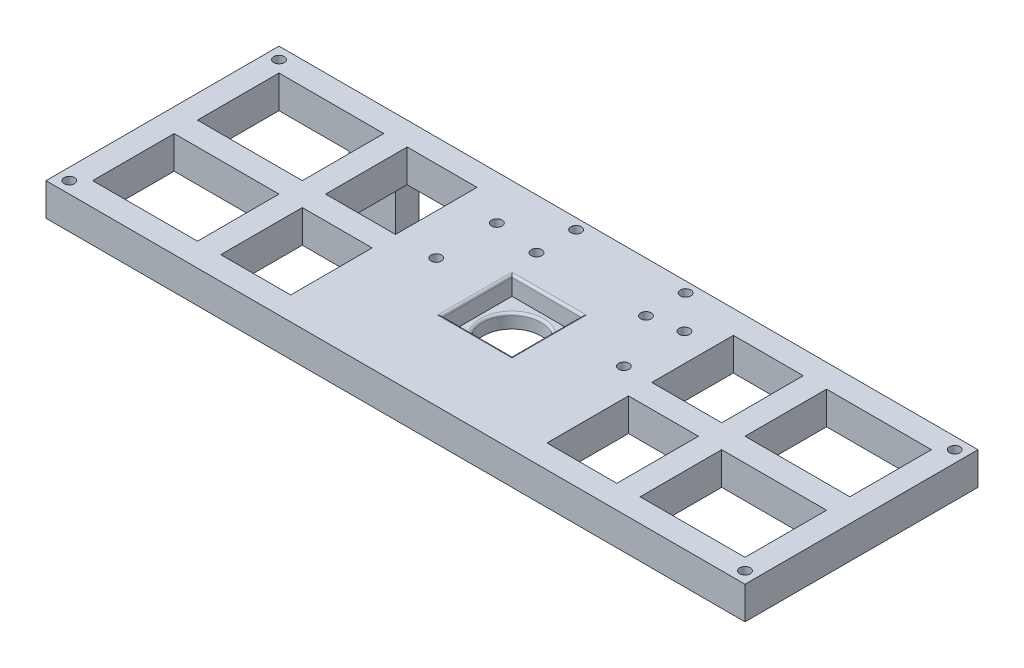
SolidWorks part; units mm, degrees
ref_plane "前视基准面" through (0, 0, 0) normal (0, 0, 1) x (1, 0, 0)
ref_plane "上视基准面" through (0, 0, 0) normal (0, 1, 0) x (1, 0, 0)
ref_plane "右视基准面" through (0, 0, 0) normal (1, 0, 0) x (0, 0, -1)
sketch "草图1" plane through (0, 0, 0) normal (0, 1, 0) x (1, 0, 0)
  line L1 (0, 0) -> (-300, 0)
  line L2 (0, 0) -> (0, 100)
  line L3 (0, 100) -> (-300, 100)
  line L4 (-300, 0) -> (-300, 100)
  dimension "D1" = 300
  dimension "D2" = 100
extrude "凸台-拉伸1" add sketch "草图1" along normal blind 16
sketch "草图2" plane through (0, 16, 0) normal (0, 1, 0) x (1, 0, 0)
  line L0 (-150, 100) -> (-150, 50) construction
  line L1 (0, 100) -> (-300, 100) construction
  line L2 (-300, 50) -> (-150, 50) construction
  line L3 (-300, 100) -> (-300, 0) construction
  line L5 (-165, 65) -> (-135, 65)
  line L6 (-165, 65) -> (-165, 35)
  line L7 (-165, 35) -> (-135, 35)
  line L8 (-135, 65) -> (-135, 35)
  line L9 (-165, 65) -> (-135, 35) construction
  line L10 (-165, 35) -> (-135, 65) construction
  dimension "D1" = 50
  dimension "D2" = 30
  dimension "D3" = 30
extrude "切除-拉伸1" cut sketch "草图2" against normal blind 8
sketch "草图3" plane through (0, 8, 0) normal (0, 1, 0) x (1, 0, 0)
  line L0 (-135, 65) -> (-165, 65) construction
  line L1 (-135, 35) -> (-135, 65) construction
  circle A0 centre (-150, 50) radius 12.5
  dimension "D3" = 25
  dimension "D1" = 15
  dimension "D2" = 15
extrude "切除-拉伸2" cut sketch "草图3" against normal blind 14
sketch "草图4" plane through (0, 16, 0) normal (0, 1, 0) x (1, 0, 0)
  line L0 (-165, 65) -> (-165, 35) construction
  line L1 (-295, 90) -> (-245, 90)
  line L2 (-295, 90) -> (-295, 55)
  line L3 (-295, 55) -> (-245, 55)
  line L4 (-245, 90) -> (-245, 55)
  line L5 (-295, 45) -> (-245, 45)
  line L6 (-295, 45) -> (-295, 10)
  line L7 (-295, 10) -> (-245, 10)
  line L8 (-245, 45) -> (-245, 10)
  line L9 (-235, 90) -> (-185, 90)
  line L10 (-235, 90) -> (-235, 55)
  line L11 (-235, 55) -> (-185, 55)
  line L12 (-185, 90) -> (-185, 55)
  line L13 (-235, 45) -> (-185, 45)
  line L14 (-235, 45) -> (-235, 10)
  line L15 (-235, 10) -> (-185, 10)
  line L16 (-185, 45) -> (-185, 10)
  line L17 (0, 100) -> (-300, 100) construction
  line L18 (-300, 0) -> (0, 0) construction
  line L19 (-300, 100) -> (-300, 0) construction
  line L20 (-150, 100) -> (-150, 73.2626) construction
  line L21 (-5, 10) -> (-55, 10)
  line L22 (-55, 45) -> (-55, 10)
  line L23 (-5, 45) -> (-55, 45)
  line L24 (-5, 45) -> (-5, 10)
  line L25 (-65, 10) -> (-115, 10)
  line L26 (-115, 45) -> (-115, 10)
  line L27 (-65, 45) -> (-115, 45)
  line L28 (-65, 45) -> (-65, 10)
  line L29 (-65, 55) -> (-115, 55)
  line L30 (-115, 90) -> (-115, 55)
  line L31 (-65, 90) -> (-115, 90)
  line L32 (-65, 90) -> (-65, 55)
  line L33 (-5, 55) -> (-55, 55)
  line L34 (-55, 90) -> (-55, 55)
  line L35 (-5, 90) -> (-55, 90)
  line L36 (-5, 90) -> (-5, 55)
  dimension "D1" = 20
  dimension "D2" = 20
  dimension "D3" = 10
  dimension "D4" = 10
  dimension "D5" = 10
  dimension "D6" = 35
  dimension "D7" = 10
  dimension "D8" = 10
  dimension "D9" = 5
  dimension "D10" = 5
  dimension "D11" = 35
  dimension "D12" = 35
  dimension "D13" = 50
  dimension "D14" = 50
  dimension "D15" = 50
  dimension "D16" = 50
extrude "切除-拉伸3" cut sketch "草图4" against normal up to next
sketch "草图7" plane through (-185, 0, 0) normal (-1, 0, 0) x (0, 0, 1)
  line L0 (-45, 0) -> (-10, 0) construction
  line L1 (-10, 0) -> (-10, 16) construction
  line L2 (-10, 16) -> (-45, 16) construction
  line L3 (-45, 16) -> (-45, 0) construction
  line L4 (-90, 0) -> (-55, 0) construction
  line L5 (-55, 0) -> (-55, 16) construction
  line L6 (-55, 16) -> (-90, 16) construction
  line L7 (-90, 16) -> (-90, 0) construction
  line L8 (-45, 0) -> (-10, 0)
  line L9 (-10, 0) -> (-10, 16)
  line L10 (-10, 16) -> (-45, 16)
  line L11 (-45, 16) -> (-45, 0)
  line L12 (-90, 0) -> (-55, 0)
  line L13 (-55, 0) -> (-55, 16)
  line L14 (-55, 16) -> (-90, 16)
  line L15 (-90, 16) -> (-90, 0)
extrude "凸台-拉伸2" add sketch "草图7" along normal blind 20
sketch "草图8" plane through (-115, 0, 0) normal (1, 0, 0) x (0, 0, -1)
  line L0 (10, 0) -> (45, 0) construction
  line L1 (45, 0) -> (45, 16) construction
  line L2 (45, 16) -> (10, 16) construction
  line L3 (10, 16) -> (10, 0) construction
  line L4 (55, 0) -> (90, 0) construction
  line L5 (90, 0) -> (90, 16) construction
  line L6 (90, 16) -> (55, 16) construction
  line L7 (55, 16) -> (55, 0) construction
  line L8 (10, 0) -> (45, 0)
  line L9 (45, 0) -> (45, 16)
  line L10 (45, 16) -> (10, 16)
  line L11 (10, 16) -> (10, 0)
  line L12 (55, 0) -> (90, 0)
  line L13 (90, 0) -> (90, 16)
  line L14 (90, 16) -> (55, 16)
  line L15 (55, 16) -> (55, 0)
extrude "凸台-拉伸3" add sketch "草图8" along normal blind 20
sketch "草图9" plane through (0, 0, 0) normal (0, -1, 0) x (1, 0, 0)
  line L5 (-295, -90) -> (-245, -90) construction
  line L10 (-260, -90) -> (-240, -90)
  line L20 (-260, -90) -> (-260, -100)
  line L21 (-260, -100) -> (-240, -100)
  line L22 (-240, -90) -> (-240, -100)
  line L23 (0, -100) -> (-300, -100) construction
  line L24 (-300, -100) -> (-300, 0) construction
  dimension "D3" = 20
  dimension "D4" = 40
extrude "凸台-拉伸4" add sketch "草图9" along normal blind 25
fillet "圆角1" radius 1 1 edges at (-150, 8, -37.5)
fillet "圆角2" radius 1 4 edges at (-135, 16, -50) (-150, 16, -65) (-150, 16, -35) (-165, 16, -50)
sketch "草图13" plane through (-5, 0, 0) normal (-1, 0, 0) x (0, 0, 1)
  line L0 (-90, 0) -> (-55, 0) construction
  line L1 (-55, 0) -> (-55, 16) construction
  line L2 (-55, 16) -> (-90, 16) construction
  line L3 (-90, 16) -> (-90, 0) construction
  line L4 (-45, 0) -> (-10, 0) construction
  line L5 (-10, 0) -> (-10, 16) construction
  line L6 (-10, 16) -> (-45, 16) construction
  line L7 (-45, 16) -> (-45, 0) construction
  line L8 (-90, 0) -> (-55, 0)
  line L9 (-55, 0) -> (-55, 16)
  line L10 (-55, 16) -> (-90, 16)
  line L11 (-90, 16) -> (-90, 0)
  line L12 (-45, 0) -> (-10, 0)
  line L13 (-10, 0) -> (-10, 16)
  line L14 (-10, 16) -> (-45, 16)
  line L15 (-45, 16) -> (-45, 0)
extrude "凸台-拉伸6" add sketch "草图13" along normal blind 4
sketch "草图14" plane through (-295, 0, 0) normal (1, 0, 0) x (0, 0, -1)
  line L0 (55, 0) -> (90, 0) construction
  line L1 (90, 0) -> (90, 16) construction
  line L2 (90, 16) -> (55, 16) construction
  line L3 (55, 16) -> (55, 0) construction
  line L4 (10, 0) -> (45, 0) construction
  line L5 (45, 0) -> (45, 16) construction
  line L6 (45, 16) -> (10, 16) construction
  line L7 (10, 16) -> (10, 0) construction
  line L8 (55, 0) -> (90, 0)
  line L9 (90, 0) -> (90, 16)
  line L10 (90, 16) -> (55, 16)
  line L11 (55, 16) -> (55, 0)
  line L12 (10, 0) -> (45, 0)
  line L13 (45, 0) -> (45, 16)
  line L14 (45, 16) -> (10, 16)
  line L15 (10, 16) -> (10, 0)
extrude "凸台-拉伸7" add sketch "草图14" along normal blind 4
sketch "草图17" plane through (-291, 0, 0) normal (1, 0, 0) x (0, 0, -1)
  line L0 (10, 16) -> (10, 0) construction
  line L1 (10, 0) -> (45, 0) construction
  line L2 (45, 0) -> (45, 16) construction
  line L3 (45, 16) -> (10, 16) construction
  line L4 (55, 16) -> (55, 0) construction
  line L5 (55, 0) -> (90, 0) construction
  line L6 (90, 0) -> (90, 16) construction
  line L7 (90, 16) -> (55, 16) construction
  line L8 (10, 16) -> (10, 0)
  line L9 (10, 0) -> (45, 0)
  line L10 (45, 0) -> (45, 16)
  line L11 (45, 16) -> (10, 16)
  line L12 (55, 16) -> (55, 0)
  line L13 (55, 0) -> (90, 0)
  line L14 (90, 0) -> (90, 16)
  line L15 (90, 16) -> (55, 16)
extrude "凸台-拉伸8" add sketch "草图17" along normal blind 1
sketch "草图18" plane through (-9, 0, 0) normal (-1, 0, 0) x (0, 0, 1)
  line L0 (-45, 16) -> (-45, 0) construction
  line L1 (-45, 0) -> (-10, 0) construction
  line L2 (-10, 0) -> (-10, 16) construction
  line L3 (-10, 16) -> (-45, 16) construction
  line L4 (-90, 16) -> (-90, 0) construction
  line L5 (-90, 0) -> (-55, 0) construction
  line L6 (-55, 0) -> (-55, 16) construction
  line L7 (-55, 16) -> (-90, 16) construction
  line L8 (-45, 16) -> (-45, 0)
  line L9 (-45, 0) -> (-10, 0)
  line L10 (-10, 0) -> (-10, 16)
  line L11 (-10, 16) -> (-45, 16)
  line L12 (-90, 16) -> (-90, 0)
  line L13 (-90, 0) -> (-55, 0)
  line L14 (-55, 0) -> (-55, 16)
  line L15 (-55, 16) -> (-90, 16)
extrude "凸台-拉伸9" add sketch "草图18" along normal blind 1
sketch "草图19" plane through (0, 16, 0) normal (0, 1, 0) x (1, 0, 0)
  line L0 (-300, 100) -> (-295, 100) construction
  line L1 (0, 100) -> (-300, 100) construction
  line L2 (-295, 100) -> (-295, 95) construction
  line L3 (-150, 100) -> (-150, 83.4567) construction
  line L4 (-300, 50) -> (-202.8605, 50) construction
  line L5 (-300, 100) -> (-300, 0) construction
  line L6 (-150, 0) -> (-150, 22.48) construction
  line L7 (-300, 0) -> (0, 0) construction
  line L8 (-5, 100) -> (-5, 95) construction
  line L9 (0, 100) -> (-5, 100) construction
  circle A0 centre (-295, 95) radius 2.25
  circle A1 centre (-295, 5) radius 2.25
  circle A4 centre (-5, 5) radius 2.25
  circle A5 centre (-5, 95) radius 2.25
  dimension "D3" = 4.5
  dimension "D1" = 5
  dimension "D2" = 5
extrude "切除-拉伸8" cut sketch "草图19" against normal blind 5
sketch "草图20" plane through (0, 0, 0) normal (0, -1, 0) x (1, 0, 0)
  circle A2 centre (-295, -95) radius 2.25 construction
  circle A3 centre (-295, -5) radius 2.25 construction
  circle A6 centre (-295, -95) radius 2.25
  circle A7 centre (-295, -5) radius 2.25
  circle A8 centre (-5, -95) radius 2.25 construction
  circle A9 centre (-5, -5) radius 2.25 construction
  circle A10 centre (-5, -95) radius 2.25
  circle A11 centre (-5, -5) radius 2.25
extrude "切除-拉伸9" cut sketch "草图20" against normal blind 7
extrude "切除-拉伸10" cut sketch "草图21" against normal blind 5
sketch "草图21" plane through (-100.2762, 16, -200.0918) normal (0, 1, 0) x (-0.0018, 0, -1)
  circle A4 centre (-104.5535, 20.9163) radius 1.45
  circle A5 centre (-121.5534, 20.9476) radius 1.45
  circle A6 centre (-121.4568, 67.9476) radius 1.45
  circle A7 centre (-104.4568, 67.9163) radius 1.45
sketch "草图22" plane through (0, 16, 0) normal (0, 1, 0) x (1, 0, 0)
  circle A0 centre (-168.0001, 95.5101) radius 2.25
  circle A1 centre (-168.0001, 78.5101) radius 2.25
  circle A2 centre (-121, 95.5) radius 2.25
  circle A3 centre (-121, 78.5) radius 2.25
  point P12 (0, 0)
  dimension "D1" = 4.5
  dimension "D2" = 4.5
  dimension "D3" = 4.5
  dimension "D4" = 4.5
extrude "切除-拉伸11" cut sketch "草图22" against normal blind 5
extrude "切除-拉伸12" cut sketch "草图23" against normal blind 5
sketch "草图23" plane through (-100.2762, 16, -200.0918) normal (0, 1, 0) x (-0.0018, 0, -1)
  circle A4 centre (-119.0792, 6.943) radius 1.45
  circle A5 centre (-145.0792, 6.9909) radius 1.45
  circle A6 centre (-144.931, 87.4716) radius 1.45
  circle A7 centre (-118.9311, 87.4237) radius 1.45
sketch "草图24" plane through (0, 16, 0) normal (0, 1, 0) x (1, 0, 0)
  circle A0 centre (-187.4808, 81) radius 2.25
  circle A1 centre (-187.4808, 55) radius 2.25
  circle A2 centre (-107, 81) radius 2.25
  circle A3 centre (-107, 55) radius 2.25
  dimension "D1" = 4.5
  dimension "D2" = 4.5
  dimension "D3" = 4.5
  dimension "D4" = 4.5
extrude "切除-拉伸13" cut sketch "草图24" against normal blind 5
sketch "草图26" plane through (0, 0, 0) normal (0, -1, 0) x (1, 0, 0)
  line L12 (-260, -90) -> (-290, -90)
  line L13 (-290, -90) -> (-290, -55)
  line L14 (-290, -55) -> (-245, -55)
  line L15 (-245, -55) -> (-245, -90)
  line L16 (-245, -90) -> (-240, -90)
  line L17 (-240, -90) -> (-240, -100)
  line L18 (-240, -100) -> (0, -100)
  line L19 (0, -100) -> (0, 0)
  line L20 (0, 0) -> (-300, 0)
  line L21 (-300, 0) -> (-300, -100)
  line L22 (-300, -100) -> (-260, -100)
  line L23 (-260, -100) -> (-260, -90)
  line L24 (-260, -90) -> (-290, -90)
  line L25 (-290, -90) -> (-290, -55)
  line L26 (-290, -55) -> (-245, -55)
  line L27 (-245, -55) -> (-245, -90)
  line L28 (-245, -90) -> (-240, -90)
  line L29 (-240, -90) -> (-240, -100)
  line L30 (-240, -100) -> (0, -100)
  line L31 (0, -100) -> (0, 0)
  line L32 (0, 0) -> (-300, 0)
  line L33 (-300, 0) -> (-300, -100)
  line L34 (-300, -100) -> (-260, -100)
  line L35 (-260, -100) -> (-260, -90)
  dimension "D1" = 0
extrude "切除-拉伸15" cut sketch "草图26" against normal blind 2
sketch "草图27" plane through (0, 11, 0) normal (0, 1, 0) x (1, 0, 0)
  circle A0 centre (-168.0001, 95.5101) radius 1.5
  circle A1 centre (-187.4808, 81) radius 1.5
  circle A2 centre (-168.0001, 78.5101) radius 1.5
  circle A3 centre (-121, 95.5) radius 1.5
  circle A4 centre (-121, 78.5) radius 1.5
  circle A5 centre (-187.4808, 55) radius 1.5
  circle A6 centre (-107, 55) radius 1.5
  circle A7 centre (-107, 81) radius 1.5
  circle A8 centre (-5, 95) radius 1.5
  circle A9 centre (-5, 5) radius 1.5
  circle A10 centre (-295, 5) radius 1.5
  circle A11 centre (-295, 95) radius 1.5
  dimension "D1" = 3
extrude "切除-拉伸16" cut sketch "草图27" against normal blind 4
